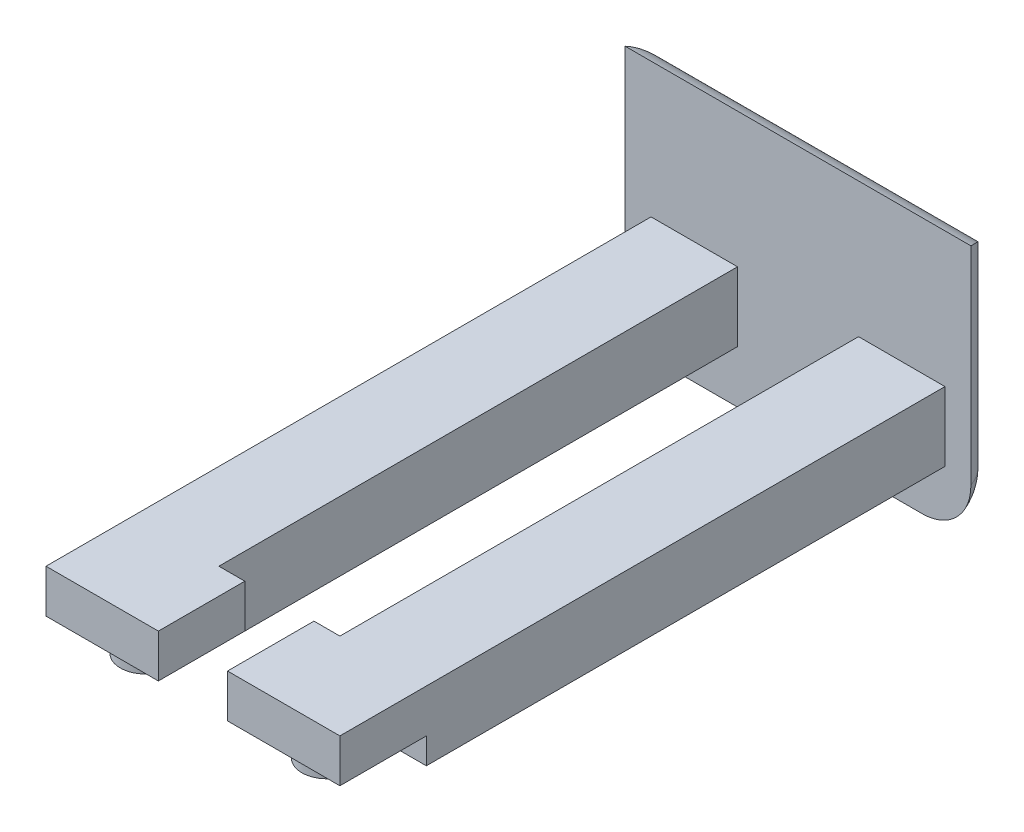
SolidWorks part; units mm, degrees
ref_plane "Front Plane" through (0, 0, 0) normal (0, 0, 1) x (1, 0, 0)
ref_plane "Top Plane" through (0, 0, 0) normal (0, 1, 0) x (1, 0, 0)
ref_plane "Right Plane" through (0, 0, 0) normal (1, 0, 0) x (0, 0, -1)
sketch "Sketch1" plane through (0, 0, 0) normal (0, 0, 1) x (1, 0, 0)
  line L1 (25.4, -19.05) -> (-25.4, -19.05)
  line L2 (25.4, -19.05) -> (25.4, 19.05)
  line L3 (25.4, 19.05) -> (-25.4, 19.05)
  line L4 (-25.4, -19.05) -> (-25.4, 19.05)
  line L5 (25.4, -19.05) -> (-25.4, 19.05) construction
  line L6 (25.4, 19.05) -> (-25.4, -19.05) construction
  point P0 (0, 0)
  dimension "D1" = 50.8
  dimension "D2" = 38.1
extrude "Boss-Extrude1" add sketch "Sketch1" along normal blind 5.08
sketch "Sketch2" plane through (0, 0, 5.08) normal (0, 0, 1) x (1, 0, 0)
  line L1 (-21.59, -0.762) -> (-5.08, -0.762)
  line L2 (-21.59, -0.762) -> (-21.59, -10.922)
  line L3 (-21.59, -10.922) -> (-5.08, -10.922)
  line L4 (-5.08, -0.762) -> (-5.08, -10.922)
  line L5 (5.08, -0.762) -> (21.59, -0.762)
  line L6 (5.08, -0.762) -> (5.08, -10.922)
  line L7 (5.08, -10.922) -> (21.59, -10.922)
  line L8 (21.59, -0.762) -> (21.59, -10.922)
  dimension "D1" = 10.16
  dimension "D2" = 19.812
  dimension "D3" = 10.16
  dimension "D4" = 3.81
  dimension "D5" = 3.81
extrude "Boss-Extrude2" add sketch "Sketch2" along normal blind 76.2
sketch "Sketch3" plane through (0, 0, 81.28) normal (0, 0, 1) x (1, 0, 0)
  line L0 (-21.59, -10.922) -> (-5.08, -10.922) construction
  line L1 (-5.08, -0.762) -> (-8.89, -0.762)
  line L2 (-5.08, -0.762) -> (-5.08, -10.922)
  line L3 (-5.08, -10.922) -> (-8.89, -10.922)
  line L4 (-8.89, -0.762) -> (-8.89, -10.922)
  line L5 (5.08, -10.922) -> (21.59, -10.922) construction
  line L6 (5.08, -0.762) -> (8.89, -0.762)
  line L7 (5.08, -0.762) -> (5.08, -10.922)
  line L8 (5.08, -10.922) -> (8.89, -10.922)
  line L9 (8.89, -0.762) -> (8.89, -10.922)
  dimension "D1" = 3.81
  dimension "D2" = 3.81
extrude "Cut-Extrude1" cut sketch "Sketch3" against normal up to surface (76.2 mm away) up to face at (0, 0, 5.08)
sketch "Sketch4" plane through (0, 0, 81.28) normal (0, 0, 1) x (1, 0, 0)
  line L0 (8.89, -10.922) -> (21.59, -10.922) construction
  line L1 (-21.59, -0.762) -> (-5.08, -0.762)
  line L2 (-21.59, -0.762) -> (-21.59, -10.922)
  line L3 (-21.59, -10.922) -> (-5.08, -10.922)
  line L4 (-5.08, -0.762) -> (-5.08, -10.922)
  line L5 (21.59, -0.762) -> (5.08, -0.762)
  line L6 (21.59, -0.762) -> (21.59, -10.922)
  line L7 (21.59, -10.922) -> (5.08, -10.922)
  line L8 (5.08, -0.762) -> (5.08, -10.922)
  dimension "D1" = 16.51
  dimension "D2" = 16.51
extrude "Boss-Extrude3" add sketch "Sketch4" along normal blind 12.7
sketch "Sketch6" plane through (0, -10.922, 0) normal (0, -1, 0) x (1, 0, 0)
  line L1 (-5.08, 81.28) -> (-21.59, 81.28)
  line L2 (-5.08, 81.28) -> (-5.08, 93.98)
  line L3 (-5.08, 93.98) -> (-21.59, 93.98)
  line L4 (-21.59, 81.28) -> (-21.59, 93.98)
  line L5 (5.08, 81.28) -> (21.59, 81.28)
  line L6 (5.08, 81.28) -> (5.08, 93.98)
  line L7 (5.08, 93.98) -> (21.59, 93.98)
  line L8 (21.59, 81.28) -> (21.59, 93.98)
extrude "Cut-Extrude2" cut sketch "Sketch6" against normal blind 3.81
sketch "Sketch5" plane through (0, -10.922, 0) normal (0, -1, 0) x (1, 0, 0)
  line L0 (-5.08, 87.63) -> (-21.59, 87.63) construction
  line L1 (-5.08, 93.98) -> (-5.08, 81.28) construction
  line L2 (-21.59, 81.28) -> (-21.59, 5.08) construction
  line L3 (5.08, 87.63) -> (21.59, 87.63) construction
  line L4 (5.08, 93.98) -> (5.08, 81.28) construction
  line L5 (21.59, 81.28) -> (21.59, 5.08) construction
  circle A0 centre (-13.335, 87.63) radius 3.683
  circle A1 centre (13.335, 87.63) radius 3.683
  dimension "D1" = 7.366
  dimension "D2" = 7.366
extrude "Boss-Extrude4" add sketch "Sketch5" against normal blind 3.81
fillet "Fillet1" radius 7.62 1 edges at (0, 19.05, 0)
fillet "Fillet4" radius 7.62 2 edges at (-25.4, -3.5921, 0) (25.4, -3.5921, 0)
fillet "Fillet7" radius 7.62 3 edges at (-22.6152, -19.05, 1.3983) (22.6152, -19.05, 1.3983) (0, -19.05, 0)
equation "\"D5@Sketch2\"=\"D4@Sketch2\""
equation "\"D2@Sketch4\"=\"D1@Sketch4\""
equation "\"D2@Sketch5\"=\"D1@Sketch5\""
